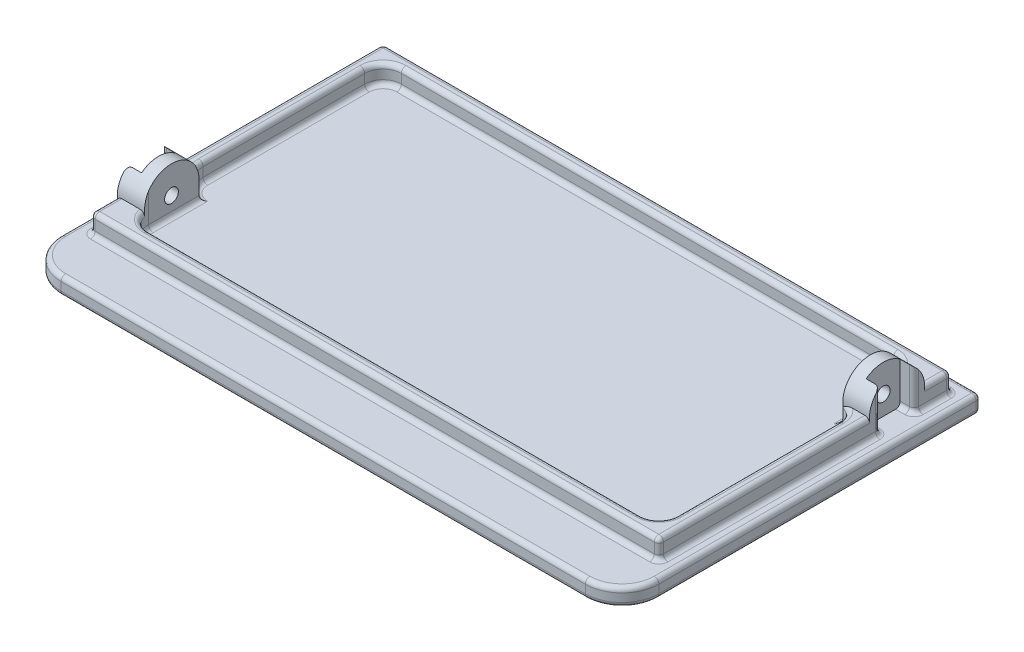
SolidWorks part; units mm, degrees
ref_plane "Alzado" through (0, 0, 0) normal (0, 0, 1) x (1, 0, 0)
ref_plane "Planta" through (0, 0, 0) normal (0, 1, 0) x (1, 0, 0)
ref_plane "Vista lateral" through (0, 0, 0) normal (1, 0, 0) x (0, 0, -1)
sketch "Croquis1" plane through (0, 0, 0) normal (0, 1, 0) x (1, 0, 0)
  line L1 (-65, -35) -> (65, -35)
  line L2 (-65, -35) -> (-65, 35)
  line L3 (-65, 35) -> (65, 35)
  line L4 (65, -35) -> (65, 35)
  line L5 (-65, -35) -> (65, 35) construction
  line L6 (-65, 35) -> (65, -35) construction
  point P0 (0, 0)
  dimension "D1" = 70
  dimension "D2" = 130
extrude "Saliente-Extruir1" add sketch "Croquis1" along normal blind 4 contours L2 L1 L4 L3
sketch "Croquis2" plane through (0, 4, 0) normal (0, 1, 0) x (1, 0, 0)
  line L0 (56, -26) -> (56, 26)
  line L1 (-62, -32) -> (62, -32)
  line L2 (-62, -32) -> (-62, 32)
  line L3 (-62, 32) -> (62, 32)
  line L4 (62, -32) -> (62, 32)
  line L5 (-62, -32) -> (62, 32) construction
  line L6 (-62, 32) -> (62, -32) construction
  line L7 (-56, 26) -> (56, 26)
  line L8 (-56, -26) -> (-56, 26)
  line L9 (-56, -26) -> (56, -26)
  line L10 (65, -35) -> (65, 35) construction
  line L11 (-65, 35) -> (65, 35) construction
  point P0 (0, 0)
  dimension "D2" = 3
  dimension "D3" = 3
  dimension "D1" = 6
extrude "Saliente-Extruir2" add sketch "Croquis2" along normal blind 4 contours L1 L4 L3 L2 L9 L8 L7 L0 region at (-60.6046, 4, 0)
sketch "Croquis3" plane through (62, 0, 0) normal (1, 0, 0) x (0, 0, -1)
  line L0 (-32, 8) -> (32, 8) construction
  line L1 (32, 8) -> (32, 4) construction
  circle A0 centre (20, 8) radius 6
  dimension "D1" = 12
  dimension "D2" = 12
extrude "Saliente-Extruir3" add sketch "Croquis3" against normal up to surface (6 mm away) up to face at (56, 6, 0)
sketch "Croquis4" plane through (-62, 0, 0) normal (-1, 0, 0) x (0, 0, 1)
  line L0 (32, 8) -> (-32, 8) construction
  line L1 (32, 8) -> (32, 4) construction
  circle A0 centre (20, 8) radius 6
  dimension "D1" = 12
  dimension "D2" = 12
extrude "Saliente-Extruir4" add sketch "Croquis4" against normal up to surface (6 mm away) up to face at (-56, 6, 0)
sketch "Croquis5" plane through (62, 0, 0) normal (1, 0, 0) x (0, 0, -1)
  circle A0 centre (20, 8) radius 1.5
  arc A1 (26, 8) -> (14, 8) centre (20, 8) ccw construction
  dimension "D1" = 3
extrude "Cortar-Extruir1" cut sketch "Croquis5" against normal up to surface (6 mm away) up to face at (56, 7.6, -2.8)
sketch "Croquis7" plane through (-62, 0, 0) normal (-1, 0, 0) x (0, 0, 1)
  circle A0 centre (20, 8) radius 1.5
  arc A1 (26, 8) -> (14, 8) centre (20, 8) ccw construction
  dimension "D1" = 3
extrude "Cortar-Extruir2" cut sketch "Croquis7" against normal up to surface (6 mm away) up to face at (-56, 7.6, 2.8)
sketch "Croquis10" plane through (0, 4, 0) normal (0, 1, 0) x (1, 0, 0)
  line L0 (-62, -32) -> (-62, 32) construction
  line L1 (-59, -23.5) -> (-62, -23.5)
  line L2 (-59, -23.5) -> (-59, -16.5)
  line L3 (-59, -16.5) -> (-62, -16.5)
  line L4 (-62, -23.5) -> (-62, -16.5)
  line L5 (-59, -23.5) -> (-62, -16.5) construction
  line L6 (-59, -16.5) -> (-62, -23.5) construction
  line L7 (-62, -14) -> (-62, -26) construction
  line L8 (62, 14) -> (62, 26) construction
  line L9 (59, 16.5) -> (62, 16.5)
  line L10 (59, 16.5) -> (59, 23.5)
  line L11 (59, 23.5) -> (62, 23.5)
  line L12 (62, 16.5) -> (62, 23.5)
  line L13 (59, 16.5) -> (62, 23.5) construction
  line L14 (59, 23.5) -> (62, 16.5) construction
  point P0 (-60.5, -20)
  point P9 (60.5, 20)
  point P16 (-62, -20)
  point P17 (62, 20)
  dimension "D1" = 3
  dimension "D2" = 3
  dimension "D3" = 7
  dimension "D4" = 7
extrude "Cortar-Extruir3" cut sketch "Croquis10" along normal blind 10
sketch "Croquis11" plane through (0, 4, 0) normal (0, 1, 0) x (1, 0, 0)
  line L0 (56, -26) -> (56, 26) construction
  line L1 (-56, -29) -> (56, -29)
  line L2 (-56, -29) -> (-56, 29)
  line L3 (-56, 29) -> (56, 29)
  line L4 (56, -29) -> (56, 29)
  line L5 (-56, -29) -> (56, 29) construction
  line L6 (-56, 29) -> (56, -29) construction
  line L7 (-62, 32) -> (62, 32) construction
  line L9 (-56, -29) -> (59, -29)
  line L10 (-56, -29) -> (-56, 14)
  line L11 (-56, 14) -> (59, 14)
  line L12 (59, -29) -> (59, 14)
  line L13 (56, 14) -> (62, 14) construction
  line L14 (-56, -14) -> (-62, -14) construction
  line L15 (-59, -14) -> (56, -14)
  line L16 (-59, -14) -> (-59, 29)
  line L17 (-59, 29) -> (56, 29)
  line L18 (56, -14) -> (56, 29)
  point P0 (0, 0)
  line M9 (-56, -26) -> (56, -26)
  line M11 (56, 26) -> (-56, 26)
  dimension "D1" = 3
extrude "Cortar-Extruir4" cut sketch "Croquis11" along normal blind 10 contours L4 L3 L2 M11 | L1 L4 L2 M9 | L10 L11 L12 L9 | L4 L3 L2 L1 | L16 L15 L18 L17 region at (0, 4, 27.5) region at (0, 4, -27.5)
sketch "Croquis9" plane through (0, 4, 0) normal (0, 1, 0) x (1, 0, 0)
  line L8 (61.8, -31.8) -> (61.8, 16.3)
  line L9 (61.8, 16.3) -> (58.8, 16.3)
  line L10 (58.8, 16.3) -> (58.8, 23.7)
  line L11 (58.8, 23.7) -> (61.8, 23.7)
  line L20 (61.8, 23.7) -> (61.8, 31.8)
  line L21 (61.8, 31.8) -> (-61.8, 31.8)
  line L22 (-61.8, 31.8) -> (-61.8, -16.3)
  line L23 (-61.8, -16.3) -> (-58.8, -16.3)
  line L24 (-58.8, -16.3) -> (-58.8, -23.7)
  line L25 (-58.8, -23.7) -> (-61.8, -23.7)
  line L26 (-61.8, -23.7) -> (-61.8, -31.8)
  line L27 (-61.8, -31.8) -> (61.8, -31.8)
  line L28 (62, -32) -> (62, 16.5)
  line L29 (-62, -32) -> (62, -32)
  line L30 (-62, -23.5) -> (-62, -32)
  line L31 (-59, -23.5) -> (-62, -23.5)
  line L32 (-59, -16.5) -> (-59, -23.5)
  line L33 (-62, -16.5) -> (-59, -16.5)
  line L34 (-62, 32) -> (-62, -16.5)
  line L35 (62, 32) -> (-62, 32)
  line L36 (62, 23.5) -> (62, 32)
  line L37 (59, 23.5) -> (62, 23.5)
  line L38 (59, 16.5) -> (59, 23.5)
  line L39 (62, 16.5) -> (59, 16.5)
  line L40 (62, -32) -> (62, 16.5)
  line L41 (-62, -32) -> (62, -32)
  line L42 (-62, -23.5) -> (-62, -32)
  line L43 (-59, -23.5) -> (-62, -23.5)
  line L44 (-59, -16.5) -> (-59, -23.5)
  line L45 (-62, -16.5) -> (-59, -16.5)
  line L46 (-62, 32) -> (-62, -16.5)
  line L47 (62, 32) -> (-62, 32)
  line L48 (62, 23.5) -> (62, 32)
  line L49 (59, 23.5) -> (62, 23.5)
  line L50 (59, 16.5) -> (59, 23.5)
  line L51 (62, 16.5) -> (59, 16.5)
  line M13 (62, 32) -> (62, 23.5)
  line M14 (62, -32) -> (-62, -32)
  line M15 (-62, -32) -> (-62, -23.5)
  line M16 (-62, 32) -> (62, 32)
  line M17 (62, 16.5) -> (62, -32)
  line M18 (-62, -23.5) -> (-59, -23.5)
  line M19 (-59, -23.5) -> (-59, -16.5)
  line M20 (-59, -16.5) -> (-62, -16.5)
  line M21 (-62, -16.5) -> (-62, 32)
  line M22 (62, 23.5) -> (59, 23.5)
  line M23 (59, 23.5) -> (59, 16.5)
  line M24 (59, 16.5) -> (62, 16.5)
  dimension "D1" = 0.2
  dimension "D2" = 0
extrude "PrintMatch" cut sketch "Croquis9" along normal through all contours L27 L26 L25 L24 L23 L22 L21 L20 L11 L10 L9 L8 M17 M24 M23 M22 M13 M16 M21 M20 M19 M18 M15 M14
sketch "Croquis12" plane through (0, 4, 0) normal (0, 1, 0) x (1, 0, 0)
  line L0 (-71.8, 41.8) -> (-71.8, -20)
  line L1 (-71.8, -20) -> (-71.8, -20)
  line L2 (-71.8, -20) -> (-71.8, -20)
  line L3 (-71.8, -20) -> (-71.8, -20)
  line L4 (-71.8, -20) -> (-71.8, -41.8)
  line L5 (-71.8, -41.8) -> (71.8, -41.8)
  line L6 (71.8, -41.8) -> (71.8, 20)
  line L7 (71.8, 20) -> (71.8, 20)
  line L8 (71.8, 20) -> (71.8, 20)
  line L9 (71.8, 20) -> (71.8, 20)
  line L10 (71.8, 20) -> (71.8, 41.8)
  line L11 (71.8, 41.8) -> (-71.8, 41.8)
  line L12 (-61.8, -31.8) -> (61.8, -31.8)
  line L13 (-61.8, -23.7) -> (-61.8, -31.8)
  line L14 (-58.8, -23.7) -> (-61.8, -23.7)
  line L15 (-58.8, -16.3) -> (-58.8, -23.7)
  line L16 (-61.8, -16.3) -> (-58.8, -16.3)
  line L17 (-61.8, 31.8) -> (-61.8, -16.3)
  line L18 (61.8, 31.8) -> (-61.8, 31.8)
  line L19 (61.8, 23.7) -> (61.8, 31.8)
  line L20 (58.8, 23.7) -> (61.8, 23.7)
  line L21 (58.8, 16.3) -> (58.8, 23.7)
  line L22 (61.8, 16.3) -> (58.8, 16.3)
  line L23 (61.8, -31.8) -> (61.8, 16.3)
  line L24 (-61.8, -31.8) -> (61.8, -31.8)
  line L25 (-61.8, -23.7) -> (-61.8, -31.8)
  line L26 (-58.8, -23.7) -> (-61.8, -23.7)
  line L27 (-58.8, -16.3) -> (-58.8, -23.7)
  line L28 (-61.8, -16.3) -> (-58.8, -16.3)
  line L29 (-61.8, 31.8) -> (-61.8, -16.3)
  line L30 (61.8, 31.8) -> (-61.8, 31.8)
  line L31 (61.8, 23.7) -> (61.8, 31.8)
  line L32 (58.8, 23.7) -> (61.8, 23.7)
  line L33 (58.8, 16.3) -> (58.8, 23.7)
  line L34 (61.8, 16.3) -> (58.8, 16.3)
  line L35 (61.8, -31.8) -> (61.8, 16.3)
  dimension "D1" = 0
  dimension "D2" = 10
extrude "Cortar-Extruir5" cut sketch "Croquis12" against normal blind 0.2
sketch "Croquis14" plane through (0, 0, 35) normal (0, 0, 1) x (1, 0, 0)
  line L4 (65, 3.8) -> (-65, 3.8)
  line L5 (-65, 3.8) -> (-65, 0)
  line L6 (-65, 0) -> (65, 0)
  line L7 (65, 0) -> (65, 3.8)
  line L8 (65, 3.8) -> (-65, 3.8)
  line L9 (-65, 3.8) -> (-65, 0)
  line L10 (-65, 0) -> (65, 0)
  line L11 (65, 0) -> (65, 3.8)
  dimension "D1" = 0
extrude "Saliente-Extruir6" add sketch "Croquis14" along normal blind 8
fillet "Redondeo7" radius 8 2 edges at (-65, 1.9, 43) (65, 1.9, 43)
fillet "Redondeo1" [suppressed] radius 8
fillet "Redondeo2" radius 4 6 edges at (56, 6, -29) (59, 6, -14) (59, 6, 29) (-56, 6, 29) (-59, 6, -29) (-59, 6, 14)
fillet "Redondeo6" radius 1 60 edges at (65, 1.9, -35) (0, 0, -35) (65, 0, 0) (-65, 1.9, -35) (-65, 0, 0) (56, 4, -19.5) (-56, 4, 19.5) (0, 8, -31.8) (65, 3.8, 0) (-59, 4, -7.4365) (-1.5, 4, -29) (59, 4, 7.4365) (1.5, 4, 29) (-65, 3.8, 0) (0, 3.8, -35) (61.8, 8, -28.9) (61.8, 3.8, 7.75) (61.8, 3.8, -27.75) (-58.1623, 8, 12.5765) (-59, 8, -7.4365) (54.4495, 8, -28.1623) (58.1623, 8, -12.5765) (59, 8, 7.4365) (-54.4495, 8, 28.1623) (-1.5, 8, -29) (-57.8284, 8, -27.8284) (1.5, 8, 29) (57.8284, 8, 27.8284) (0, 8, 31.8) (0, 3.8, 31.8) (61.8, 8, 8.9) (61.8, 5.9, 31.8) (61.8, 5.9, -31.8) (0, 3.8, -31.8) (-61.8, 5.9, -31.8) (-61.8, 8, -8.9) (-61.8, 3.8, -7.75) (-61.8, 3.8, 27.75) (-61.8, 8, 28.9) (-57.8284, 4, -27.8284) (54.8284, 4, -27.8284) (58.1623, 4, -12.5765) (57.8284, 4, 27.8284) (-54.8284, 4, 27.8284) (-58.1623, 4, 12.5765) (0, 0, 43) (-61.8, 5.9, 31.8) (0, 3.8, 43) (60.3, 3.8, -23.7) (60.3, 3.8, -16.3) (-60.3, 3.8, 16.3) (-60.3, 3.8, 23.7) (61.8, 8.2617, -23.7) (61.8, 8.2617, -16.3) (-61.8, 8.2617, 16.3) (-61.8, 8.2617, 23.7) (62.6569, 3.8, 40.6569) (-62.6569, 3.8, 40.6569) (62.6569, 0, 40.6569) (-62.6569, 0, 40.6569)
